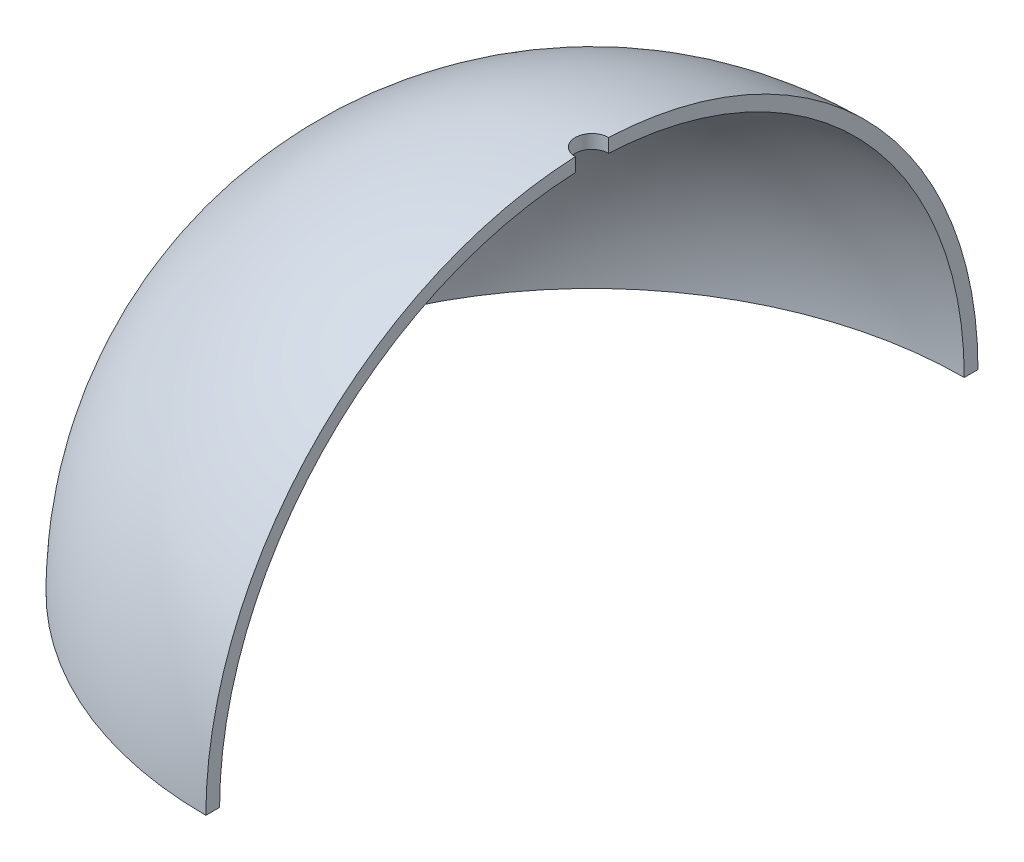
SolidWorks part; units mm, degrees
ref_plane "Front" through (0, 0, 0) normal (0, 0, 1) x (1, 0, 0)
ref_plane "Top" through (0, 0, 0) normal (0, 1, 0) x (1, 0, 0)
ref_plane "Right" through (0, 0, 0) normal (1, 0, 0) x (0, 0, -1)
sketch "Sketch1" plane through (0, 0, 0) normal (0, 1, 0) x (1, 0, 0)
  line L0 (0, 9275) -> (0, 8945)
  line L1 (0, -8945) -> (0, -9275)
  line L3 (0, -41.7154) -> (0, 43.2806) construction
  arc A0 (0, 8945) -> (0, -8945) centre (0, 0) ccw
  arc A1 (0, 9275) -> (0, -9275) centre (0, 0) ccw
  dimension "D1" = 8945
  dimension "D2" = 9275
  dimension "D3" = 330
revolve "Revolve1" add sketch "Sketch1" angle 90 about L3
sketch "Sketch5" plane through (0, 0, 0) normal (0, 1, 0) x (1, 0, 0)
  circle A0 centre (0, 0) radius 400
extrude "Cut-Extrude2" cut sketch "Sketch5" along normal up to surface (9266.3706 mm away) contours A0 up to face at (-4637.5, 4637.5, 0)
